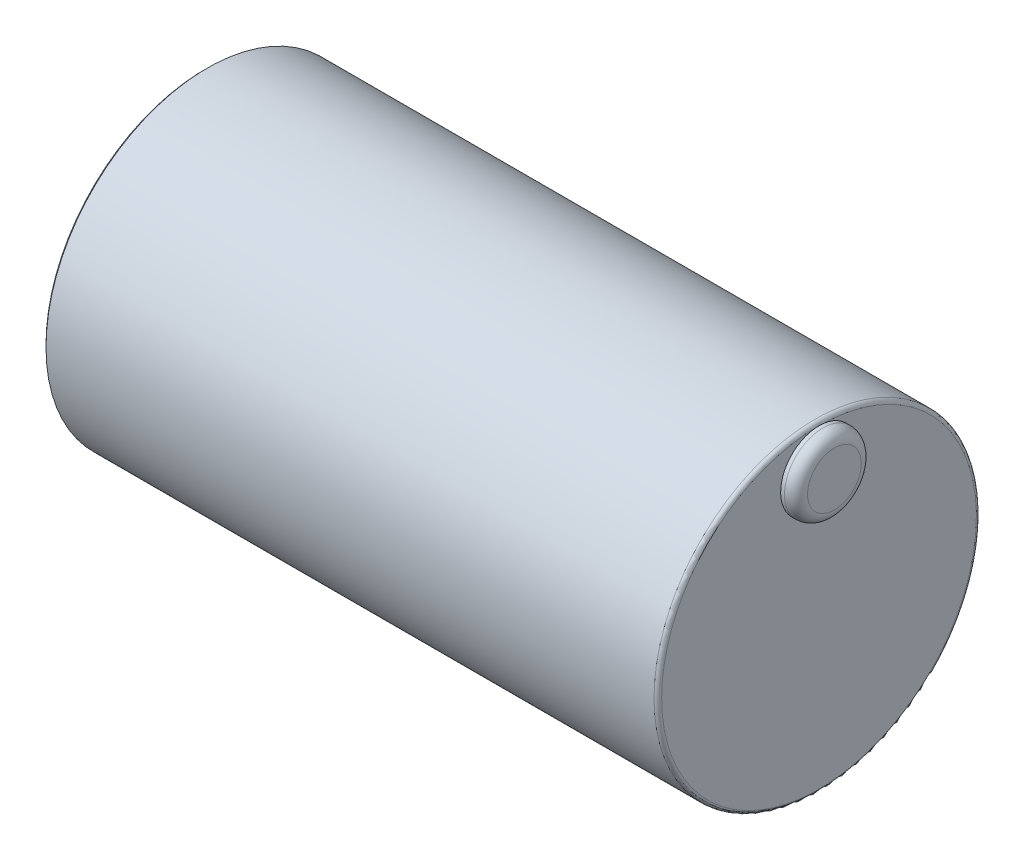
SolidWorks part; units mm, degrees
ref_plane "Plan de face" through (0, 0, 0) normal (0, 0, 1) x (1, 0, 0)
ref_plane "Plan de dessus" through (0, 0, 0) normal (0, 1, 0) x (1, 0, 0)
ref_plane "Plan de droite" through (0, 0, 0) normal (1, 0, 0) x (0, 0, -1)
sketch "Esquisse1" plane through (0, 0, 0) normal (0, 0, 1) x (1, 0, 0)
  line L0 (-33.7551, 0) -> (33.5102, 0) construction
  line L1 (0, 22) -> (0, -23.3878) construction
  line L2 (0, 0) -> (0, 11)
  line L3 (0, 11) -> (2, 11)
  line L4 (2, 11) -> (2, 21)
  line L5 (2, 21) -> (82, 21)
  line L6 (82, 21) -> (82, 0)
  line L7 (82, 0) -> (0, 0)
  dimension "D1" = 2
  dimension "D2" = 42
  dimension "D3" = 22
  dimension "D4" = 80
revolve "Révolution1" add sketch "Esquisse1" angle 360 about L0
chamfer "Chanfrein1" distance 0.3 angle 45 2 edges at (0, 0, 11) (2, 0, 21)
fillet "Congé1" radius 0.5 1 edges at (82, 0, 21)
sketch "Esquisse2" plane through (82, 0, 0) normal (1, 0, 0) x (0, 0, -1)
  line L0 (0, 32.9323) -> (0, -34.5163) construction
  circle A0 centre (0, 15.5) radius 5
  circle A1 centre (0, 0) radius 20.5 construction
  dimension "D1" = 10
extrude "Boss.-Extru.1" add sketch "Esquisse2" along normal blind 2
fillet "Congé2" radius 1.5 1 edges at (84, 15.5, -5)
hole_wizard "Trou pour taraudage pour trou taraudé M41" positions "Esquisse3" profile "Esquisse4" hole size "M4" standard "ISO"
sketch "Esquisse3" plane through (2, 0, 0) normal (-1, 0, 0) x (0, 0, 1)
  line L0 (0, -25.8661) -> (0, 26.5366) construction
  circle A0 centre (0, 0) radius 16 construction
  point P0 (0, 16)
  dimension "D1" = 32
sketch "Esquisse4" plane through (2, 16, 0) normal (0, 1, 0) x (0, 0, 1)
  line L0 (0, 0) -> (0, 8.9914)
  line L1 (0, 8.9914) -> (1.65, 8)
  line L2 (1.65, 8) -> (1.65, 0)
  line L5 (1.65, 0) -> (0, 0)
  line L10 (0, 8.9914) -> (-1.65, 8) construction
  line L11 (0, -6.35) -> (0, 107.95) construction
  dimension "Diamètre du perçage" = 3.3
  dimension "Profondeur du perçage" = 8
  dimension "Angle de pointe" = 118
ref_axis "Axe1" through (2, 0, 0) along (-1, 0, 0)
pattern_circular "Répétition circulaire1" count 4 over 360 about axis through (2, 0, 0) along (-1, 0, 0) of "Trou pour taraudage pour trou taraudé M41"
